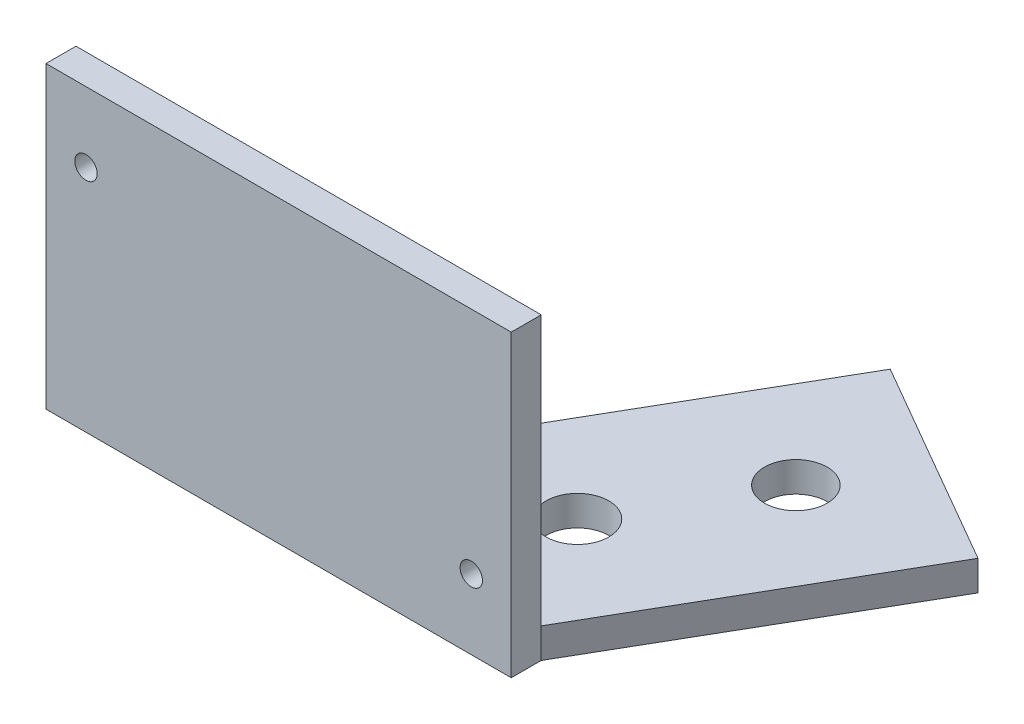
SolidWorks part; units mm, degrees
ref_plane "Front Plane" through (0, 0, 0) normal (0, 0, 1) x (1, 0, 0)
ref_plane "Top Plane" through (0, 0, 0) normal (0, 1, 0) x (1, 0, 0)
ref_plane "Right Plane" through (0, 0, 0) normal (1, 0, 0) x (0, 0, -1)
sketch "Sketch1" plane through (0, 0, 0) normal (0, 0, 1) x (1, 0, 0)
  line L1 (0, 0) -> (33.782, 0) construction
  line L2 (0, 0) -> (0, 19.812) construction
  line L3 (0, 19.812) -> (33.782, 19.812) construction
  line L4 (33.782, 0) -> (33.782, 19.812) construction
  line L5 (-1.5875, -1.5875) -> (35.3695, -1.5875)
  line L6 (-1.5875, -1.5875) -> (-1.5875, 19.812)
  line L7 (-1.5875, 19.812) -> (35.3695, 19.812)
  line L8 (35.3695, -1.5875) -> (35.3695, 19.812)
  circle A0 centre (1.5875, 14.2558) radius 0.889
  circle A1 centre (32.1945, 1.5875) radius 0.889
  dimension "D3" = 1.778
  dimension "D4" = 1.778
  dimension "D5" = 1.5875
  dimension "D6" = 1.5875
  dimension "D7" = 1.5875
  dimension "D8" = 5.5562
  dimension "D9" = 3.175
  dimension "D11" = 3.175
  dimension "D12" = 5.5562
  dimension "D1" = 19.812
  dimension "D2" = 33.782
  dimension "D10" = 3.175
extrude "Boss-Extrude1" add sketch "Sketch1" along normal blind 2.3813
sketch "Sketch2" plane through (0, -1.5875, 0) normal (0, -1, 0) x (1, 0, 0)
  line L8 (-1.5875, 0) -> (35.3695, 0) construction
  line L9 (-1.5875, 2.3813) -> (35.3695, 2.3813)
  line L10 (-1.5875, 2.3813) -> (-1.5875, 0)
  line L12 (35.3695, 2.3813) -> (35.3695, 0)
  line L15 (48.0695, -21.997) -> (31.5717, -31.522)
  line L17 (48.0695, -21.997) -> (35.3695, 0)
  line L19 (31.5717, -31.522) -> (13.3725, 0)
  line L20 (13.3725, 0) -> (-1.5875, 0)
  dimension "D1" = 19.05
  dimension "D2" = 25.4
  dimension "D3" = 60
extrude "Boss-Extrude3" add sketch "Sketch2" along normal blind 2.3813
sketch "Sketch4" plane through (0, -1.5875, 0) normal (0, 1, 0) x (1, 0, 0)
  line L0 (39.8206, 26.7595) -> (35.801, 19.7973) construction
  line L2 (35.801, 19.7973) -> (29.451, 8.7988) construction
  line L3 (29.451, 8.7988) -> (24.371, 0) construction
  line L5 (48.0695, 21.997) -> (31.5717, 31.522) construction
  line L6 (35.3695, 0) -> (13.3725, 0) construction
  circle A0 centre (35.801, 19.7973) radius 2.4892
  circle A1 centre (29.451, 8.7988) radius 2.4892
  point P10 (24.371, 0)
  point P15 (39.8206, 26.7595)
  dimension "D1" = 4.9784
  dimension "D2" = 12.7
  dimension "D3" = 10.16
extrude "Cut-Extrude2" cut sketch "Sketch4" against normal up to next
